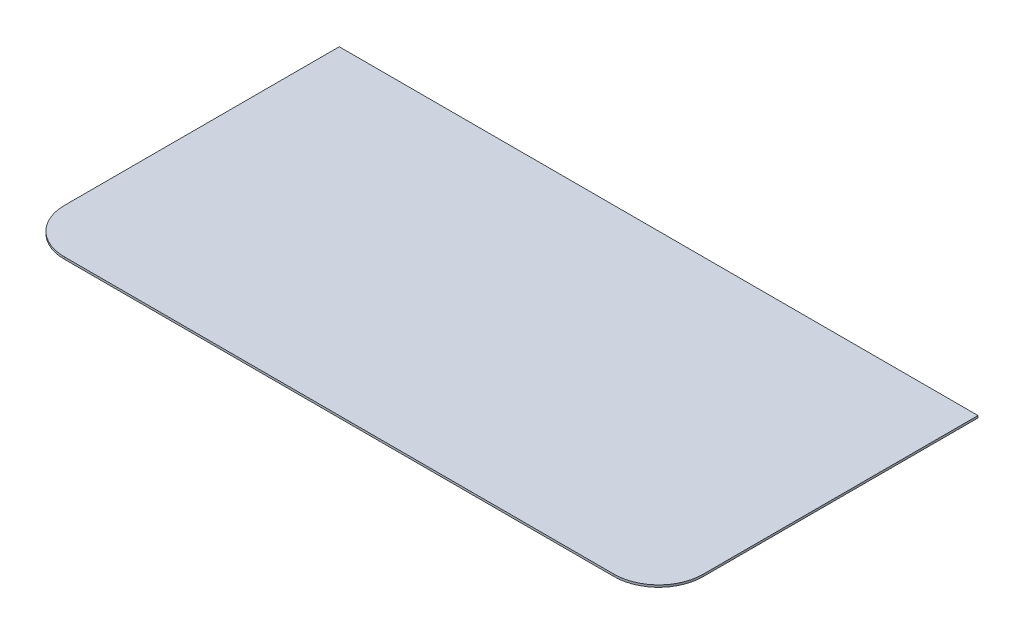
SolidWorks part; units mm, degrees
ref_plane "Ebene vorne" through (0, 0, 0) normal (0, 0, 1) x (1, 0, 0)
ref_plane "Ebene oben" through (0, 0, 0) normal (0, 1, 0) x (1, 0, 0)
ref_plane "Ebene rechts" through (0, 0, 0) normal (1, 0, 0) x (0, 0, -1)
sketch "Skizze1" plane through (0, 0, 0) normal (0, 1, 0) x (1, 0, 0)
  line L0 (0, 0) -> (0, 151)
  line L2 (151, 151) -> (151, 0)
  line L3 (0, 0) -> (151, 0)
  line L6 (151, 151) -> (0, 151)
  dimension "D2" = 151
extrude "Linear austragen1" add sketch "Skizze1" along normal blind 1
fillet "Verrundung1" radius 21 1 edges at (151, 0.5, 0)
mirror "Spiegeln1" about plane through (0, 1, 0) normal (1, 0, 0) of "Linear austragen1", "Verrundung1"
